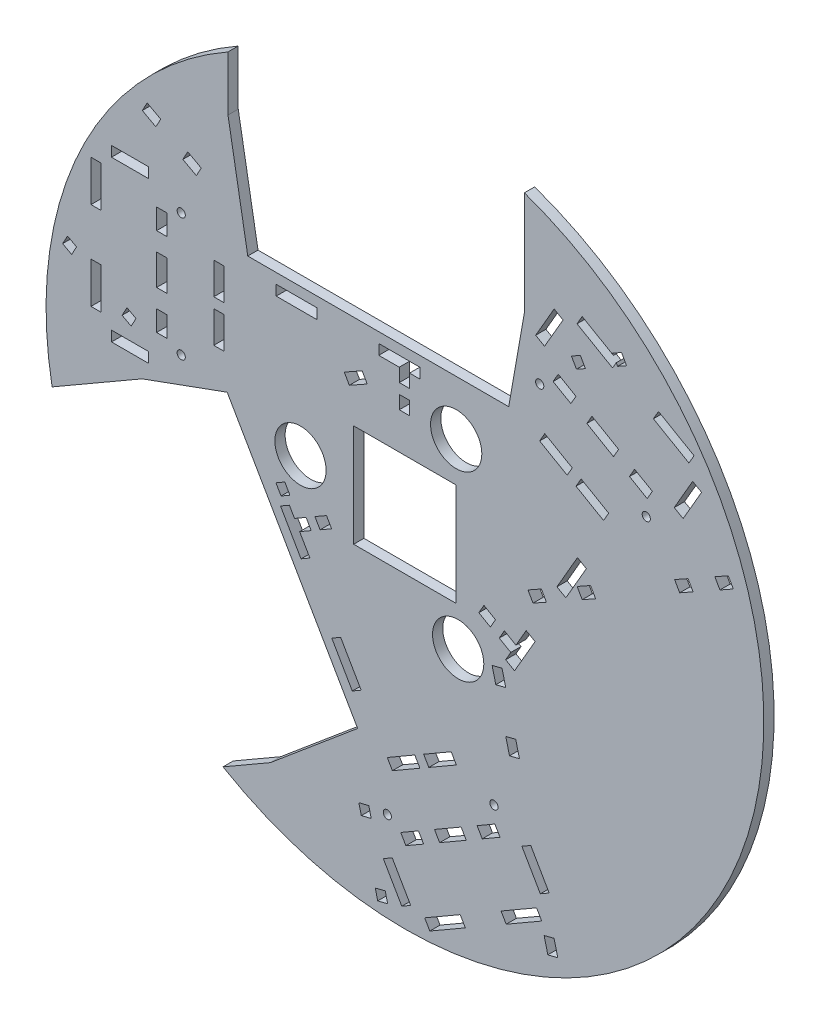
SolidWorks part; units mm, degrees
material "Balsa"
ref_plane "Plan de face" through (0, 0, 0) normal (0, 0, 1) x (1, 0, 0)
ref_plane "Plan de dessus" through (0, 0, 0) normal (0, 1, 0) x (1, 0, 0)
ref_plane "Plan de droite" through (0, 0, 0) normal (1, 0, 0) x (0, 0, -1)
sketch "Esquisse1" plane through (0, 0, 0) normal (0, 0, 1) x (1, 0, 0)
  circle A0 centre (148.0804, -12.1102) radius 175
  dimension "D1" = 350
extrude "Boss.-Extru.1" add sketch "Esquisse1" along normal blind 5
sketch "Esquisse2" plane through (0, 0, 5) normal (0, 0, 1) x (1, 0, 0)
  line L0 (135.3118, 53.7774) -> (135.3118, 48.7774)
  line L1 (5, 72.2774) -> (23, 72.2774)
  line L2 (5, 72.2774) -> (5, 67.2774)
  line L3 (5, 67.2774) -> (23, 67.2774)
  line L4 (23, 72.2774) -> (23, 67.2774)
  line L5 (-5, 62.2774) -> (0, 62.2774)
  line L6 (-5, 62.2774) -> (-5, 42.2774)
  line L7 (-5, 42.2774) -> (0, 42.2774)
  line L8 (0, 62.2774) -> (0, 42.2774)
  line L9 (-5, 19.2774) -> (0, 19.2774)
  line L10 (-5, 19.2774) -> (-5, -0.7226)
  line L11 (-5, -0.7226) -> (0, -0.7226)
  line L12 (0, 19.2774) -> (0, -0.7226)
  line L13 (5, -5.7226) -> (23, -5.7226)
  line L14 (5, -5.7226) -> (5, -10.7226)
  line L15 (5, -10.7226) -> (23, -10.7226)
  line L16 (23, -5.7226) -> (23, -10.7226)
  line L17 (27, 14.2774) -> (32, 14.2774)
  line L18 (27, 14.2774) -> (27, 4.2774)
  line L19 (27, 4.2774) -> (32, 4.2774)
  line L20 (32, 14.2774) -> (32, 4.2774)
  line L21 (27, 38.2774) -> (32, 38.2774)
  line L22 (27, 38.2774) -> (27, 23.2774)
  line L23 (27, 23.2774) -> (32, 23.2774)
  line L24 (32, 38.2774) -> (32, 23.2774)
  line L25 (27, 57.2774) -> (32, 57.2774)
  line L26 (27, 57.2774) -> (27, 47.2774)
  line L27 (27, 47.2774) -> (32, 47.2774)
  line L28 (32, 57.2774) -> (32, 47.2774)
  line L29 (54.86, 48.7774) -> (59.86, 48.7774)
  line L30 (54.86, 48.7774) -> (54.86, 33.2774)
  line L31 (54.86, 33.2774) -> (59.86, 33.2774)
  line L32 (59.86, 48.7774) -> (59.86, 33.2774)
  line L33 (54.86, 28.2774) -> (59.86, 28.2774)
  line L34 (54.86, 28.2774) -> (54.86, 12.7774)
  line L35 (54.86, 12.7774) -> (59.86, 12.7774)
  line L36 (59.86, 28.2774) -> (59.86, 12.7774)
  line L37 (85.3118, 53.7774) -> (105.3118, 53.7774)
  line L38 (85.3118, 53.7774) -> (85.3118, 48.7774)
  line L39 (85.3118, 48.7774) -> (105.3118, 48.7774)
  line L40 (105.3118, 53.7774) -> (105.3118, 48.7774)
  line L41 (145.3118, 37.2774) -> (150.3118, 37.2774)
  line L42 (145.3118, 37.2774) -> (145.3118, 30.7774)
  line L43 (145.3118, 30.7774) -> (150.3118, 30.7774)
  line L44 (150.3118, 37.2774) -> (150.3118, 30.7774)
  line L45 (135.3118, 48.7774) -> (145.3118, 48.7774)
  line L46 (155.3118, 48.7774) -> (135.3118, 48.7774) construction
  line L47 (145.3118, 48.7774) -> (145.3118, 42.2774)
  line L48 (145.3118, 42.2774) -> (150.3118, 42.2774)
  line L49 (150.3118, 42.2774) -> (150.3118, 48.7774)
  line L50 (150.3118, 48.7774) -> (155.3118, 48.7774)
  line L51 (155.3118, 48.7774) -> (155.3118, 53.7774)
  line L52 (155.3118, 53.7774) -> (135.3118, 53.7774)
  line L53 (292.7025, 69.6073) -> (283.7025, 54.0188)
  line L54 (292.7025, 69.6073) -> (288.3723, 72.1073)
  line L55 (288.3723, 72.1073) -> (279.3723, 56.5188)
  line L56 (283.7025, 54.0188) -> (279.3723, 56.5188)
  line L57 (289.0422, 83.2676) -> (286.5422, 78.9374)
  line L58 (289.0422, 83.2676) -> (271.7217, 93.2676)
  line L59 (271.7217, 93.2676) -> (269.2217, 88.9374)
  line L60 (286.5422, 78.9374) -> (269.2217, 88.9374)
  line L61 (251.8031, 104.7676) -> (249.3031, 100.4374)
  line L62 (251.8031, 104.7676) -> (234.4826, 114.7676)
  line L63 (234.4826, 114.7676) -> (231.9826, 110.4374)
  line L64 (249.3031, 100.4374) -> (231.9826, 110.4374)
  line L65 (225.1525, 108.6073) -> (216.1525, 93.0188)
  line L66 (225.1525, 108.6073) -> (220.8223, 111.1073)
  line L67 (220.8223, 111.1073) -> (211.8223, 95.5188)
  line L68 (216.1525, 93.0188) -> (211.8223, 95.5188)
  line L69 (231.473, 79.5547) -> (228.973, 75.2246)
  line L70 (231.473, 79.5547) -> (222.8127, 84.5547)
  line L71 (222.8127, 84.5547) -> (220.3127, 80.2246)
  line L72 (228.973, 75.2246) -> (220.3127, 80.2246)
  line L73 (252.2576, 67.5547) -> (249.7576, 63.2246)
  line L74 (252.2576, 67.5547) -> (239.2672, 75.0547)
  line L75 (239.2672, 75.0547) -> (236.7672, 70.7246)
  line L76 (249.7576, 63.2246) -> (236.7672, 70.7246)
  line L77 (268.7121, 58.0547) -> (266.2121, 53.7246)
  line L78 (268.7121, 58.0547) -> (260.0518, 63.0547)
  line L79 (260.0518, 63.0547) -> (257.5518, 58.7246)
  line L80 (266.2121, 53.7246) -> (257.5518, 58.7246)
  line L81 (247.4209, 38.1773) -> (244.9209, 33.8472)
  line L82 (247.4209, 38.1773) -> (233.9975, 45.9273)
  line L83 (233.9975, 45.9273) -> (231.4975, 41.5972)
  line L84 (244.9209, 33.8472) -> (231.4975, 41.5972)
  line L85 (229.6673, 48.4273) -> (227.1673, 44.0972)
  line L86 (229.6673, 48.4273) -> (216.2439, 56.1773)
  line L87 (216.2439, 56.1773) -> (213.7439, 51.8472)
  line L88 (227.1673, 44.0972) -> (213.7439, 51.8472)
  line L89 (211.5251, -33.996) -> (207.195, -31.496)
  line L90 (236.5251, 9.3053) -> (226.5251, -8.0153)
  line L91 (236.5251, 9.3053) -> (232.195, 11.8053)
  line L92 (232.195, 11.8053) -> (222.195, -5.5153)
  line L93 (226.5251, -8.0153) -> (222.195, -5.5153)
  line L94 (192.2357, -34.4063) -> (189.7357, -38.7364)
  line L95 (192.2357, -34.4063) -> (186.6065, -31.1563)
  line L96 (186.6065, -31.1563) -> (184.1065, -35.4864)
  line L97 (189.7357, -38.7364) -> (184.1065, -35.4864)
  line L98 (207.195, -31.496) -> (202.195, -40.1563)
  line L99 (202.195, -40.1563) -> (196.5658, -36.9063)
  line L100 (196.5658, -36.9063) -> (194.0658, -41.2364)
  line L101 (194.0658, -41.2364) -> (199.695, -44.4864)
  line L102 (199.695, -44.4864) -> (197.195, -48.8165)
  line L103 (197.195, -48.8165) -> (201.5251, -51.3165)
  line L104 (201.5251, -51.3165) -> (211.5251, -33.996)
  line L105 (146.5388, -178.2153) -> (137.5388, -162.6268)
  line L106 (146.5388, -178.2153) -> (150.869, -175.7153)
  line L107 (150.869, -175.7153) -> (141.869, -160.1268)
  line L108 (137.5388, -162.6268) -> (141.869, -160.1268)
  line L109 (160.1991, -181.8755) -> (157.6991, -177.5454)
  line L110 (160.1991, -181.8755) -> (177.5196, -171.8755)
  line L111 (177.5196, -171.8755) -> (175.0196, -167.5454)
  line L112 (157.6991, -177.5454) -> (175.0196, -167.5454)
  line L113 (197.4382, -160.3755) -> (194.9382, -156.0454)
  line L114 (197.4382, -160.3755) -> (214.7587, -150.3755)
  line L115 (214.7587, -150.3755) -> (212.2587, -146.0454)
  line L116 (194.9382, -156.0454) -> (212.2587, -146.0454)
  line L117 (214.0888, -139.2153) -> (205.0888, -123.6268)
  line L118 (214.0888, -139.2153) -> (218.4189, -136.7153)
  line L119 (218.4189, -136.7153) -> (209.4189, -121.1268)
  line L120 (205.0888, -123.6268) -> (209.4189, -121.1268)
  line L121 (185.7683, -130.1627) -> (183.2683, -125.8326)
  line L122 (185.7683, -130.1627) -> (194.4286, -125.1627)
  line L123 (194.4286, -125.1627) -> (191.9286, -120.8326)
  line L124 (183.2683, -125.8326) -> (191.9286, -120.8326)
  line L125 (164.9837, -142.1627) -> (162.4837, -137.8326)
  line L126 (164.9837, -142.1627) -> (177.9741, -134.6627)
  line L127 (177.9741, -134.6627) -> (175.4741, -130.3326)
  line L128 (162.4837, -137.8326) -> (175.4741, -130.3326)
  line L129 (148.5292, -151.6627) -> (146.0292, -147.3326)
  line L130 (148.5292, -151.6627) -> (157.1895, -146.6627)
  line L131 (157.1895, -146.6627) -> (154.6895, -142.3326)
  line L132 (146.0292, -147.3326) -> (154.6895, -142.3326)
  line L133 (141.9604, -123.2852) -> (139.4604, -118.9551)
  line L134 (141.9604, -123.2852) -> (155.3838, -115.5352)
  line L135 (155.3838, -115.5352) -> (152.8838, -111.2051)
  line L136 (139.4604, -118.9551) -> (152.8838, -111.2051)
  line L137 (159.7139, -113.0352) -> (157.2139, -108.7051)
  line L138 (159.7139, -113.0352) -> (173.1373, -105.2852)
  line L139 (173.1373, -105.2852) -> (170.6373, -100.9551)
  line L140 (157.2139, -108.7051) -> (170.6373, -100.9551)
  line L141 (97.4044, -56.1119) -> (101.7345, -53.6119)
  line L142 (122.4044, -99.4132) -> (112.4044, -82.0927)
  line L143 (122.4044, -99.4132) -> (126.7345, -96.9132)
  line L144 (126.7345, -96.9132) -> (116.7345, -79.5927)
  line L145 (112.4044, -82.0927) -> (116.7345, -79.5927)
  line L146 (106.6938, -39.2017) -> (104.1938, -34.8716)
  line L147 (106.6938, -39.2017) -> (112.323, -35.9517)
  line L148 (112.323, -35.9517) -> (109.823, -31.6216)
  line L149 (104.1938, -34.8716) -> (109.823, -31.6216)
  line L150 (101.7345, -53.6119) -> (96.7345, -44.9517)
  line L151 (96.7345, -44.9517) -> (102.3637, -41.7017)
  line L152 (102.3637, -41.7017) -> (99.8637, -37.3716)
  line L153 (99.8637, -37.3716) -> (94.2345, -40.6216)
  line L154 (94.2345, -40.6216) -> (91.7345, -36.2914)
  line L155 (91.7345, -36.2914) -> (87.4044, -38.7914)
  line L156 (87.4044, -38.7914) -> (97.4044, -56.1119)
  line L157 (135.3118, 53.7774) -> (135.3118, 48.7774) construction
  line L158 (105.3118, 53.7774) -> (135.3118, 53.7774) construction
  point P83 (148.0804, -12.1102)
  point P192 (148.0804, -12.1102)
  point P193 (148.0804, -12.1102)
  dimension "D1" = 3
extrude "Enlèv. mat.-Extru.1" cut sketch "Esquisse2" against normal blind 5
sketch "Esquisse6" plane through (0, 0, 5) normal (0, 0, 1) x (1, 0, 0)
  line L0 (93.9998, -7.2151) -> (100.2998, -18.127) construction
  line L1 (206.3213, 102.2219) -> (206.3213, 185.5637)
  line L2 (123.0804, -37.1102) -> (173.0804, -37.1102)
  line L3 (123.0804, -37.1102) -> (123.0804, 12.8898)
  line L4 (123.0804, 12.8898) -> (173.0804, 12.8898)
  line L5 (173.0804, -37.1102) -> (173.0804, 12.8898)
  line L6 (123.0804, -37.1102) -> (173.0804, 12.8898) construction
  line L7 (123.0804, 12.8898) -> (173.0804, -37.1102) construction
  line L8 (206.3213, 185.5637) -> (61.7972, 185.5637)
  line L9 (61.7972, 113.4862) -> (71.4438, 58.7774)
  line L10 (71.4438, 58.7774) -> (198.6608, 58.7774)
  line L11 (198.6608, 58.7774) -> (206.3213, 102.2219)
  line L12 (61.7972, 185.5637) -> (61.7972, 113.4862)
  line L13 (19.9456, -18.8381) -> (-52.2306, -60.5091)
  line L14 (-52.2306, -60.5091) -> (20.0314, -185.6706)
  line L15 (82.4524, -149.6318) -> (125.0083, -113.9232)
  line L16 (125.0083, -113.9232) -> (61.3998, -3.7501)
  line L17 (61.3998, -3.7501) -> (19.9456, -18.8381)
  line L18 (20.0314, -185.6706) -> (82.4524, -149.6318)
  line L19 (87.4044, -38.7914) -> (97.4044, -56.1119) construction
  circle A0 centre (173.06, 32.2774) radius 12.5
  circle A1 centre (174.0314, -55.9369) radius 12.5
  circle A2 centre (97.1498, -12.671) radius 12.5
  point P2 (148.0804, -12.1102)
  point P8 (148.0804, -12.1102)
  point P10 (148.0804, -12.1102)
  point P35 (148.0804, -12.1102)
  dimension "D2" = 25
  dimension "D3" = 50
  dimension "D4" = 50
  dimension "D5" = 70.8876
  dimension "D6" = 50.5804
  dimension "D7" = 127.217
  dimension "D8" = 100
  dimension "D9" = 100
  dimension "D10" = 54.7088
  dimension "D11" = 43.4444
  dimension "D1" = 3
  dimension "D12" = 2
extrude "Enlèv. mat.-Extru.6" cut sketch "Esquisse6" against normal blind 5
hole_wizard "Trous de centrage Ø4.0mm1" positions "Esquisse7" profile "Esquisse8" hole size "Ø4.0" standard "Ansi Metric" end condition through all
sketch "Esquisse7" plane through (148.0804, -12.1102, -78) normal (0, 0, -1) x (1, 0, 0)
  point P0 (65.7012, -88.0226)
  point P3 (117.6627, -58.0226)
  point P6 (-109.0804, -72.8876)
  point P9 (-109.0804, -12.8876)
  point P12 (-8.5823, 130.9102)
  point P15 (43.3792, 100.9102)
sketch "Esquisse8" plane through (213.7816, 75.9124, -78) normal (1, 0, 0) x (0, 1, 0)
  line L0 (0, 0) -> (0, 83)
  line L1 (0, 83) -> (2, 83)
  line L2 (2, 83) -> (2, 0)
  line L3 (2, 0) -> (0, 0)
  line L4 (0, -6.35) -> (0, 107.95) construction
  dimension "Diamètre du perçage jusqu'au prochain" = 4
  dimension "Profondeur du perçage jusqu'au prochain" = 83
sketch "Esquisse9" plane through (0, 0, 5) normal (0, 0, 1) x (1, 0, 0)
  line L0 (301.6473, 32.8747) -> (299.2005, 37.2351)
  line L1 (301.6473, 32.8747) -> (308.1879, 36.5449)
  line L2 (299.2005, 37.2351) -> (305.7411, 40.9053)
  line L3 (308.1879, 36.5449) -> (305.7411, 40.9053)
  line L4 (282.0254, 21.8642) -> (279.5786, 26.2246)
  line L5 (282.0254, 21.8642) -> (288.566, 25.5344)
  line L6 (279.5786, 26.2246) -> (286.1192, 29.8948)
  line L7 (288.566, 25.5344) -> (286.1192, 29.8948)
  line L8 (241.0375, -1.1356) -> (238.5907, 3.2248)
  line L9 (241.0375, -1.1356) -> (234.4969, -4.8058)
  line L10 (238.5907, 3.2248) -> (232.0501, -0.4454)
  line L11 (234.4969, -4.8058) -> (232.0501, -0.4454)
  line L12 (214.6084, -10.2326) -> (217.0552, -14.593)
  line L13 (214.6084, -10.2326) -> (208.0678, -13.9027)
  line L14 (217.0552, -14.593) -> (210.5146, -18.2632)
  line L15 (208.0678, -13.9027) -> (210.5146, -18.2632)
  line L16 (217.0552, -14.593) -> (234.4969, -4.8058) construction
  line L17 (214.6084, -10.2326) -> (217.0552, -14.593) construction
  line L18 (256.1275, 104.7997) -> (251.7671, 102.3529)
  line L19 (256.1275, 104.7997) -> (253.6807, 109.1601)
  line L20 (251.7671, 102.3529) -> (249.3203, 106.7133)
  line L21 (253.6807, 109.1601) -> (249.3203, 106.7133)
  line L22 (236.0696, 93.5445) -> (231.7091, 91.0977)
  line L23 (236.0696, 93.5445) -> (233.6228, 97.9049)
  line L24 (231.7091, 91.0977) -> (229.2624, 95.4581)
  line L25 (233.6228, 97.9049) -> (229.2624, 95.4581)
  line L26 (129.6754, 33.8428) -> (120.9546, 28.9492)
  line L27 (129.6754, 33.8428) -> (127.2286, 38.2032)
  line L28 (120.9546, 28.9492) -> (118.5078, 33.3096)
  line L29 (127.2286, 38.2032) -> (118.5078, 33.3096)
  line L30 (256.1275, 104.7997) -> (120.9546, 28.9492) construction
  line L31 (301.6473, 32.8747) -> (217.0552, -14.593) construction
  line L32 (-16.4384, 23.2791) -> (-12.0459, 20.8904)
  line L33 (-16.4384, 23.2791) -> (-18.8272, 18.8866)
  line L34 (-12.0459, 20.8904) -> (-14.4347, 16.4979)
  line L35 (-18.8272, 18.8866) -> (-14.4347, 16.4979)
  line L36 (12.552, 7.5136) -> (16.9445, 5.1249)
  line L37 (12.552, 7.5136) -> (10.1633, 3.1211)
  line L38 (16.9445, 5.1249) -> (14.5558, 0.7324)
  line L39 (10.1633, 3.1211) -> (14.5558, 0.7324)
  line L44 (22.4127, 98.9071) -> (29.0015, 95.324)
  line L45 (22.4127, 98.9071) -> (20.024, 94.5146)
  line L46 (29.0015, 95.324) -> (26.6128, 90.9315)
  line L47 (20.024, 94.5146) -> (26.6128, 90.9315)
  line L48 (42.179, 88.1579) -> (48.7677, 84.5748)
  line L49 (42.179, 88.1579) -> (39.7903, 83.7654)
  line L50 (48.7677, 84.5748) -> (46.379, 80.1823)
  line L51 (39.7903, 83.7654) -> (46.379, 80.1823)
  line L53 (148.0804, -12.1102) -> (9.6568, -109.2191) construction
  line L55 (130.4208, 187.6926) -> (148.0804, -12.1102) construction
  arc A0 (59.3693, -162.9589) -> (206.3213, 152.9141) centre (148.0804, -12.1102) ccw construction
  line B0 (154.106, -73.5915) -> (185.6214, -199.5155) construction
  line B1 (126.7996, -149.8343) -> (125.5857, -144.9839)
  line B2 (130.4361, -143.77) -> (125.5857, -144.9839)
  line B3 (131.65, -148.6204) -> (126.7996, -149.8343)
  line B4 (131.65, -148.6204) -> (130.4361, -143.77)
  line B5 (134.8115, -181.8469) -> (133.5976, -176.9965)
  line B6 (138.448, -175.7826) -> (133.5976, -176.9965)
  line B7 (139.6619, -180.633) -> (134.8115, -181.8469)
  line B8 (139.6619, -180.633) -> (138.448, -175.7826)
  line B9 (190.562, -54.5014) -> (195.4124, -53.2875)
  line B10 (197.2333, -60.5631) -> (195.4124, -53.2875)
  line B11 (192.3829, -61.777) -> (190.562, -54.5014)
  line B12 (192.3829, -61.777) -> (197.2333, -60.5631)
  line B13 (202.089, -79.9647) -> (197.2386, -81.1786)
  line B14 (199.0595, -88.4542) -> (197.2386, -81.1786)
  line B15 (203.9099, -87.2403) -> (202.089, -79.9647)
  line B16 (203.9099, -87.2403) -> (199.0595, -88.4542)
  line B17 (222.6043, -161.9364) -> (217.7539, -163.1503)
  line B18 (215.933, -155.8747) -> (217.7539, -163.1503)
  line B19 (220.7834, -154.6608) -> (222.6043, -161.9364)
  line B20 (220.7834, -154.6608) -> (215.933, -155.8747)
  dimension "D9" = 170.2546
  dimension "D1" = 10
  dimension "D2" = 5
  dimension "D3" = 7.5
  dimension "D4" = 7.5
  dimension "D5" = 7.5
  dimension "D6" = 7.5
  dimension "D7" = 5
  dimension "D8" = 117
  dimension "D10" = 167.3371
  dimension "D11" = 69
sketch_block_instance "Bloc1-1"
sketch_block "Bloc1"
extrude "Holes catchers of glass" cut sketch "Esquisse9" against normal blind 10
sketch "Esquisse10" plane through (0, 0, 5) normal (0, 0, 1) x (1, 0, 0)
  line L0 (89.4961, -27.6144) -> (91.9961, -31.9445)
  line L1 (89.4961, -27.6144) -> (85.1672, -30.1137)
  line L2 (91.9961, -31.9445) -> (87.6672, -34.4438)
  line L3 (85.1672, -30.1137) -> (87.6672, -34.4438)
  dimension "D1" = 4.9986
extrude "Holes boards servo" cut sketch "Esquisse10" against normal blind 10
